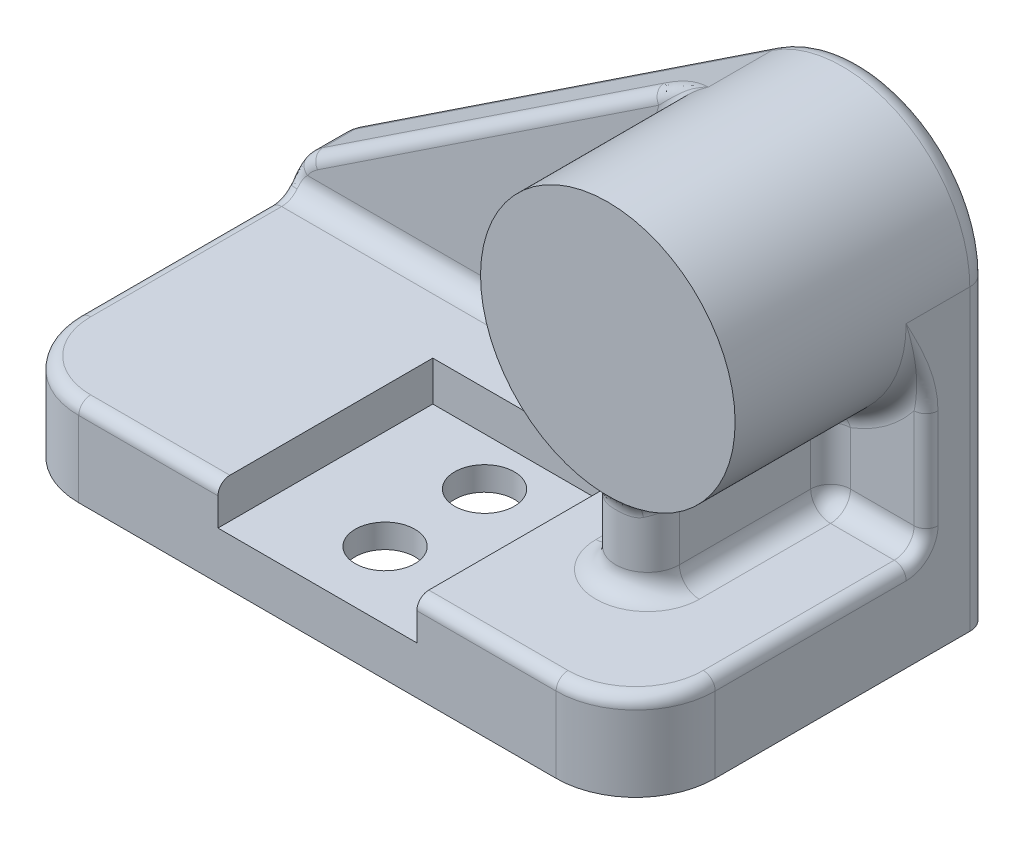
SolidWorks part; units mm, degrees
note: The reader was unsure of these and kept them because the rebuilt part matched: shared geometry of "Contour Selection<6>".
material "Plain Carbon Steel"
ref_plane "Front" through (0, 0, 0) normal (0, 0, 1) x (1, 0, 0)
ref_plane "Top" through (0, 0, 0) normal (0, 1, 0) x (1, 0, 0)
ref_plane "Right" through (0, 0, 0) normal (1, 0, 0) x (0, 0, -1)
sketch "Sketch1" plane through (0, 0, 0) normal (0, 1, 0) x (1, 0, 0)
  line L0 (0, 0) -> (160, 0)
  line L1 (0, 0) -> (0, 89)
  line L2 (0, 89) -> (160, 89)
  line L3 (160, 89) -> (160, 0)
  dimension "D1" = 89
  dimension "D4" = 160
extrude "Base_Plate" add sketch "Sketch1" along normal blind 22
fillet "Base_Fillet" radius 20 2 edges at (0, 11, 0) (160, 11, 0)
sketch "Contour Selection" plane through (3.6004, 22, -17.5327) normal (0, 1, 0) x (-1, 0, 0)
  line L0 (-76.3996, 17.5327) -> (-76.3996, -67.0852) construction
  line L1 (-16.3996, 17.5327) -> (-136.3996, 17.5327) construction
  line L2 (3.6004, -71.4673) -> (-156.3996, -71.4673) construction
  line L4 (-51.3996, 17.5327) -> (-101.3996, 17.5327)
  line L5 (-51.3996, 17.5327) -> (-51.3996, -36.4673)
  line L6 (-51.3996, -36.4673) -> (-101.3996, -36.4673)
  line L7 (-101.3996, 17.5327) -> (-101.3996, -36.4673)
  circle A0 centre (-76.3996, 0.5327) radius 7.5
  circle A1 centre (-76.3996, -24.4673) radius 7.5
  dimension "D3" = 15
  dimension "D4" = 25
  dimension "D5" = 12
  dimension "D1" = 35
  dimension "D2" = 50
extrude "Hole_Mtg" cut sketch "Contour Selection" against normal blind 10 contours L5 L6 L7 L4
shell "Wall_Thickness" thickness 6
extrude "Thru_Holes" cut sketch "Contour Selection<6>" against normal through all contours A0 | A1
sketch "Contour Selection<6>" plane through (3.6004, 22, -17.5327) normal (0, 1, 0) x (-1, 0, 0) same geometry as "Contour Selection"
sketch "Sketch2" plane through (0, 0, -89) normal (0, 0, -1) x (-1, 0, 0)
  line L1 (-20, 0) -> (-140, 0) construction
  line L2 (-160, 22) -> (0, 22) construction
  line L3 (-160, 22) -> (0, 22)
  line L4 (-160, 22) -> (-160, 0) construction
  line L5 (-160, 22) -> (-160, 75)
  line L6 (-5.3632, 31.9976) -> (-110.3018, 101.6603)
  arc A0 (-110.3018, 101.6603) -> (-160, 75) centre (-128, 75) ccw
  arc A1 (0, 22) -> (-5.3632, 31.9976) centre (-12, 22) ccw
  dimension "D1" = 64
  dimension "D4" = 12
  dimension "D2" = 75
extrude "Vertical_Plate" add sketch "Sketch2" against normal blind 16
sketch "Sketch3" plane through (0, 0, -89) normal (0, 0, -1) x (-1, 0, 0)
  circle A0 centre (-128, 75) radius 32
  arc A1 (-110.3018, 101.6603) -> (-160, 75) centre (-128, 75) ccw construction
extrude "Circular_Boss" add sketch "Sketch3" against normal blind 64
sketch "Sketch4" plane through (0, 22, 0) normal (0, 1, 0) x (-1, 0, 0)
  line L0 (-96, -25) -> (-160, -25) construction
  line L1 (-96, -73) -> (-160, -73) construction
  line L2 (-120, -73) -> (-120, -35)
  line L3 (-128, -73) -> (-128, -89) construction
  line L5 (-136, -73) -> (-136, -35)
  line L7 (-136, -73) -> (-120, -73)
  arc A0 (-120, -35) -> (-136, -35) centre (-128, -35) ccw
  dimension "D2" = 8
  dimension "D1" = 2
extrude "Rib_Under" add sketch "Sketch4" along normal up to next
fillet "Rib_Fillet" radius 5 7 edges at (120, 44.0161, -54) (120, 22, -54) (127.1921, 43.0102, -27.0409) (128, 22, -27) (136, 22, -54) (136, 44.0161, -54)
fillet "Circ_Fillet" radius 5 18 edges at (96.206, 71.3753, -73) (136, 33.6795, -73) (137.4645, 23.4645, -73) (136.89, 43.2065, -73) (120, 33.6795, -73) (118.5355, 23.4645, -73) (119.11, 43.2065, -73) (160, 37.5, -89) (0, 11, -89) (1.4255, 27.6726, -89) (57.8325, 66.829, -89) (143.1271, 103.1988, -89) (154.3038, 56.7762, -73)
fillet "Fillet1" radius 3 13 edges at (102.007, 96.1539, -71.5835) (50.0951, 61.6926, -73) (37.5, 22, 0) (5.8579, 22, -5.8579) (0.0498, 23.0921, -71.1191) (160, 65.0439, -71.5835) (122.5, 22, 0) (160, 23.4645, -71.5355) (154.1421, 22, -5.8579)
